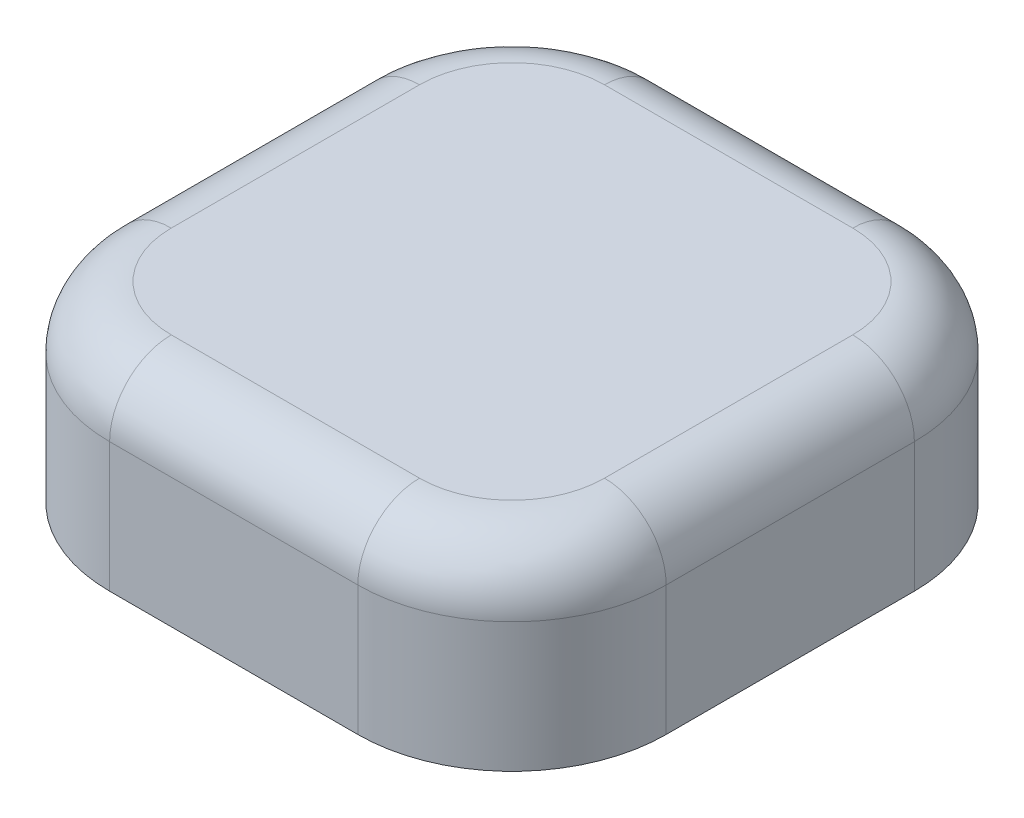
SolidWorks part; units mm, degrees
ref_plane "前视基准面" through (0, 0, 0) normal (0, 0, 1) x (1, 0, 0)
ref_plane "上视基准面" through (0, 0, 0) normal (0, 1, 0) x (1, 0, 0)
ref_plane "右视基准面" through (0, 0, 0) normal (1, 0, 0) x (0, 0, -1)
other "Configuration Table"
sketch "草图1" plane through (0, 0, 0) normal (0, 1, 0) x (1, 0, 0)
  line L0 (-2.2, 0) -> (2.2, 0) construction
  line L1 (0, 2.2) -> (0, -2.2) construction
  line L2 (2.2, 0.6) -> (2.2, -0.6)
  line L3 (-0.6, 2.2) -> (0.6, 2.2)
  line L4 (-2.2, -0.6) -> (-2.2, 0.6)
  line L5 (-0.6, -2.2) -> (0.6, -2.2)
  line L6 (-0.6, 2.2) -> (-0.6, 0.6)
  line L7 (-0.6, 0.6) -> (-2.2, 0.6)
  line L8 (-2.2, -0.6) -> (-0.6, -0.6)
  line L9 (-0.6, -0.6) -> (-0.6, -2.2)
  line L10 (0.6, -2.2) -> (0.6, -0.6)
  line L11 (0.6, -0.6) -> (2.2, -0.6)
  line L12 (2.2, 0.6) -> (0.6, 0.6)
  line L13 (0.6, 0.6) -> (0.6, 2.2)
  circle A0 centre (0, 0) radius 2.8
  point P4 (0, 0)
  point P7 (0, 0)
  point P10 (2.2, 0)
  point P13 (0, 2.2)
  point P16 (-2.2, 0)
  point P19 (0, -2.2)
  dimension "D7" = 5.6
  dimension "D1" = 4.4
  dimension "D2" = 4.4
  dimension "D3" = 1.2
  dimension "D4" = 1.2
  dimension "D5" = 1.2
  dimension "D6" = 1.2
extrude "凸台-拉伸1" add sketch "草图1" against normal blind 5
sketch "草图2" plane through (0, 0, 0) normal (0, 1, 0) x (1, 0, 0)
  line L0 (0, -9.025) -> (0, 9.025) construction
  line L1 (-9.025, 9.025) -> (9.025, 9.025)
  line L2 (-9.025, -9.025) -> (9.025, -9.025)
  line L3 (-9.025, 9.025) -> (-9.025, -9.025)
  line L4 (9.025, 9.025) -> (9.025, -9.025)
  point P4 (0, 0)
  point P8 (0, 9.025)
  point P11 (0, -9.025)
  dimension "D1" = 18.05
  dimension "D2" = 18.05
extrude "凸台-拉伸2" add sketch "草图2" along normal blind 1.2
sketch "草图3" plane through (0, 0, 0) normal (0, 1, 0) x (1, 0, 0)
  line L4 (9.025, -9.025) -> (9.025, 9.025)
  line L5 (-9.025, -9.025) -> (9.025, -9.025)
  line L6 (-9.025, 9.025) -> (-9.025, -9.025)
  line L7 (9.025, 9.025) -> (-9.025, 9.025)
  line L8 (9.025, -9.025) -> (9.025, 9.025)
  line L9 (-9.025, -9.025) -> (9.025, -9.025)
  line L10 (-9.025, 9.025) -> (-9.025, -9.025)
  line L11 (9.025, 9.025) -> (-9.025, 9.025)
  line L20 (7.825, -7.825) -> (7.825, 7.825)
  line L21 (7.825, 7.825) -> (-7.825, 7.825)
  line L22 (-7.825, 7.825) -> (-7.825, -7.825)
  line L23 (-7.825, -7.825) -> (7.825, -7.825)
  line L24 (7.825, -7.825) -> (7.825, 7.825)
  line L25 (7.825, 7.825) -> (-7.825, 7.825)
  line L26 (-7.825, 7.825) -> (-7.825, -7.825)
  line L27 (-7.825, -7.825) -> (7.825, -7.825)
  dimension "D1" = 0
  dimension "D2" = 1.2
extrude "凸台-拉伸3" add sketch "草图3" against normal blind 5
fillet "圆角3" radius 5 8 edges at (7.825, -2.5, 7.825) (-7.825, -2.5, 7.825) (-7.825, -2.5, -7.825) (7.825, -2.5, -7.825) (-9.025, -1.9, 9.025) (9.025, -1.9, 9.025) (9.025, -1.9, -9.025) (-9.025, -1.9, -9.025)
fillet "圆角4" radius 2 16 edges at (-7.5605, 1.2, -7.5605) (0, 1.2, -9.025) (7.5605, 1.2, -7.5605) (9.025, 1.2, 0) (7.5605, 1.2, 7.5605) (0, 1.2, 9.025) (-7.5605, 1.2, 7.5605) (-9.025, 1.2, 0) (-7.825, 0, 0) (0, 0, -7.825) (7.825, 0, 0) (0, 0, 7.825) (-6.3605, 0, -6.3605) (6.3605, 0, -6.3605) (6.3605, 0, 6.3605) (-6.3605, 0, 6.3605)
chamfer "倒角1" distance 0.5 angle 45 1 edges at (0, 0, 2.8)
